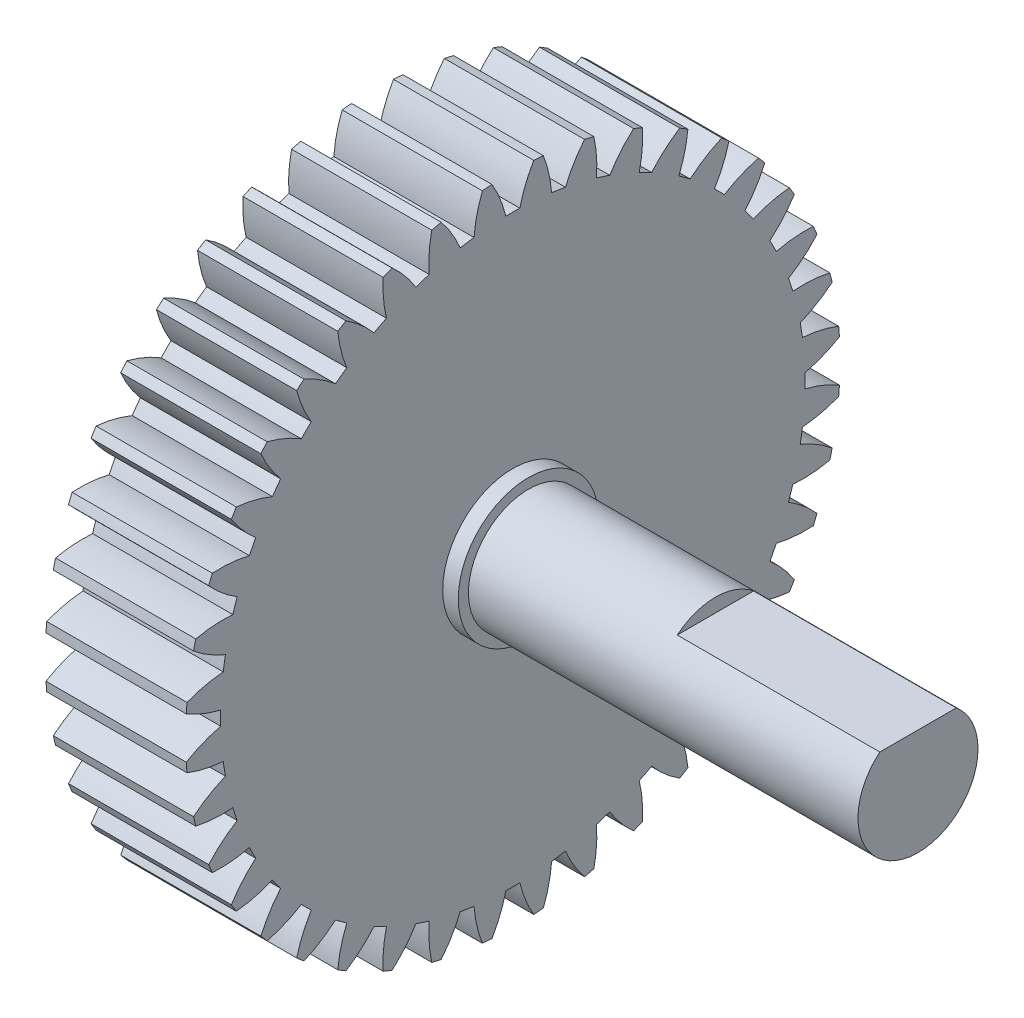
SolidWorks part; units mm, degrees
ref_plane "Plane1" through (0, 0, 0) normal (0, 0, 1) x (1, 0, 0)
ref_plane "Plane2" through (0, 0, 0) normal (0, 1, 0) x (1, 0, 0)
ref_plane "Plane3" through (0, 0, 0) normal (1, 0, 0) x (0, 0, -1)
sketch "HoldingSke" plane through (0, 0, 0) normal (0, 1, 0) x (1, 0, 0)
  line L0 (0, 0) -> (0.766, -0.6428)
  line L1 (-15, 0) -> (100, 0) construction
  line L2 (0, 0) -> (-2.1039, 2.3779)
  line L3 (0, 0) -> (-11.863, 4.5341)
  line L4 (0, 0) -> (6.6156, 5.5511)
  line L5 (0, 0) -> (-46.8476, -17.4728)
  line L6 (0, 0) -> (-7.4607, -5.0337)
  line L7 (-2.1039, 2.3779) -> (8.6586, 51.2059)
  line L8 (-76.2, 54.61) -> (-75.5, 54.61)
  line L9 (-71.009, 38.7566) -> (-53.1078, 45.2721)
  line L10 (-76.2, 71.12) -> (104.1128, 71.12)
  line L11 (0, 0) -> (-9, 0)
  line L12 (-76.2, 101.6) -> (-76.162, 101.6)
  line L13 (24.9733, 27.94) -> (52.9518, 28.4284)
  line L14 (24.9733, 27.94) -> (24.9743, 27.94)
  line L15 (24.9733, 27.94) -> (100.4006, 29.5858)
  line L16 (-63.627, -1) -> (-12.827, -1)
  circle A0 centre (0, 0) radius 2
  circle A1 centre (0, 0) radius 18.749
  circle A2 centre (0, 0) radius 37.5
  circle A3 centre (0, 0) radius 2
  dimension "MHD" = 37.498
  dimension "Hub_dia" = 75
  dimension "Bore" = 4
  dimension "MBD" = 4
  dimension "Num_teeth" = 40
  dimension "Pitch" = 1
  dimension "Overall_len" = 50
  dimension "Show_teeth" = 40
  dimension "Thickness" = 9
  dimension "OAL" = 50.0001
  dimension "T_dim" = 0.7
  dimension "Ap" = 20
  dimension "H" = 19.05
  dimension "Pitch_radius" = 180.3128
  dimension "Width" = 9
  dimension "Backlash" = 0.038
  dimension "Addendum_fac" = 1
  dimension "Dedendum_fac" = 1.25
  dimension "Clearance_fac" = 0.25
  dimension "Dedendum_add" = 0.001
  dimension "Module" = 1
sketch "BasProSke" plane through (0, 0, 0) normal (0, 1, 0) x (1, 0, 0)
  line L0 (-10, 0) -> (60, 0) construction
  line L1 (0, 0) -> (0, 21)
  line L2 (0, 0) -> (9, 0)
  line L3 (9, 0) -> (9, 21)
  line L4 (9, 21) -> (0, 21)
  dimension "Thickness" = 9
  dimension "Diameter" = 42
revolve "Base-Revolve" add sketch "BasProSke" angle 360 about L0
sketch "TooCutSke" plane through (0, 0, 0) normal (1, 0, 0) x (0, 0, -1)
  line L1 (0, 0) -> (0, 107) construction
  line L2 (0, 0) -> (-0.8517, 19.9819) construction
  line L3 (0, 0) -> (-3.1363, 39.8509) construction
  line L4 (-0.8517, 19.9819) -> (-1.5682, 19.9255) construction
  arc A0 (0.4487, 18.7436) -> (-0.4487, 18.7436) centre (0, 0) ccw
  arc A1 (1.3547, 20.9817) -> (-1.3547, 20.9817) centre (0, 0) ccw
  circle A2 centre (0, 0) radius 20 construction
  circle A3 centre (0, 0) radius 18.7939 construction
  arc A4 (-0.4487, 18.7436) -> (-1.3547, 20.9817) centre (-8.2322, 16.895) ccw
  arc A5 (1.3547, 20.9817) -> (0.4487, 18.7436) centre (8.2322, 16.895) ccw
  dimension "Root_dia" = 37.498
  dimension "Overcut_dia" = 42.0508
  dimension "Pitch_dia" = 40
  dimension "Base_dia" = 37.5877
  dimension "Flank_rad" = 8
  dimension "Half_ang" = 4.5
  dimension "Half_CT" = 0.7187
extrude "ToothCut" cut sketch "TooCutSke" along normal through all
fillet "Breaks" [suppressed] radius 0.02 tangent propagation no
fillet "RootFillets" [suppressed] radius 0.251
pattern_circular "TeethCuts" count 40 every 9 about axis through (-10, 0, 0) along (1, 0, 0) of "ToothCut", "RootFillets", "Breaks"
sketch "HubNeaOneSke" plane through (0, 0, 0) normal (-1, 0, 0) x (0, 0, 1)
  circle A0 centre (0, 0) radius 18.749
  dimension "Diameter" = 37.498
extrude "HubNearOne" [suppressed] add sketch "HubNeaOneSke" along normal blind 41.0001
sketch "HubNeaBotSke" plane through (0, 0, 0) normal (-1, 0, 0) x (0, 0, 1)
  circle A0 centre (0, 0) radius 18.749
  dimension "Diameter" = 37.498
extrude "HubNearBoth" [suppressed] add sketch "HubNeaBotSke" along normal blind 20.5
ref_plane "FarPln" through (9, 0, 0) normal (1, 0, 0) x (0, 0, -1)
sketch "HubFarSke" plane through (9, 0, 0) normal (1, 0, 0) x (0, 0, -1)
  circle A0 centre (0, 0) radius 18.749
  dimension "Diameter" = 37.498
extrude "HubFar" [suppressed] add sketch "HubFarSke" along normal blind 20.5
sketch "BorSke" plane through (0, 0, 0) normal (1, 0, 0) x (0, 0, -1)
  circle A0 centre (0, 0) radius 2
  dimension "Diameter" = 4
extrude "Bore" cut sketch "BorSke" along normal mid plane 100.0001
sketch "KeySke" plane through (0, 0, 0) normal (1, 0, 0) x (0, 0, -1)
  line L0 (-0.8, 0) -> (-0.8, 2.7)
  line L1 (-0.8, 2.7) -> (0.8, 2.7)
  line L2 (0.8, 2.7) -> (0.8, 0)
  line L3 (0, 0) -> (0, 34) construction
  line L4 (-0.8, 0) -> (0.8, 0)
  dimension "Offset" = 2.7
  dimension "Width" = 1.6
extrude "Keyway" [suppressed] cut sketch "KeySke" along normal mid plane 100.0001
pattern_circular "Keyway2" [suppressed] count 2 every 90 about axis through (-10, 0, 0) along (1, 0, 0) reverse direction yes
sketch "Sketch1" plane through (9, 0, 0) normal (1, 0, 0) x (0, 0, -1)
  line L0 (-2.45, 2.9698) -> (2.45, 2.9698)
  circle A0 centre (0, 0) radius 4.5
  circle A1 centre (0, 0) radius 3.85
  dimension "D1" = 4.9
  dimension "D2" = 7.7
  dimension "D3" = 9
extrude "Boss-Extrude1" add sketch "Sketch1" along normal blind 26 and the other way blind 9 contours L0 A1 region at (9, -0.2248, 0)
extrude "Boss-Extrude2" add sketch "Sketch1<3>" along normal blind 13 and the other way blind 9 contours L0 A1 region at (9, 3.3256, 0)
sketch "Sketch1<3>" plane through (9, 0, 0) normal (1, 0, 0) x (0, 0, -1) same geometry as "Sketch1"
extrude "Boss-Extrude3" add sketch "Sketch1<4>" along normal blind 1 contours A0 A1 region at (9, 0, 4.3727)
sketch "Sketch1<4>" plane through (9, 0, 0) normal (1, 0, 0) x (0, 0, -1) same geometry as "Sketch1"
equation "' \"Module@HoldingSke\" = 6.35"
equation "' \"Num_teeth@HoldingSke\" = 12"
equation "' \"Ap@HoldingSke\" =  20"
equation "' \"Ap@HoldingSke\" = 20"
equation "' \"Width@HoldingSke\" = 0.5 * 25.4"
equation "' \"Hub_dia@HoldingSke\"= 1 * 25.4"
equation "' \"Hub_dia@HoldingSke\" = 1 * 25.4"
equation "' \"Overall_len@HoldingSke\" = 1.0 * 25.4"
equation "' \"Bore@HoldingSke\" = 0.75 * 25.4"
equation "' \"T_dim@HoldingSke\" = 0.1 * 25.4"
equation "' \"Width@KeySke\" = 0.25 * 25.4"
equation "' \"Show_teeth@HoldingSke\" = 13"
equation "' \"Backlash@HoldingSke\" = 0.009 * 25.4"
equation "' \"Addendum_fac@HoldingSke\" = 1.0"
equation "' \"Dedendum_fac@HoldingSke\" = 1.25"
equation "' \"Dedendum_add@HoldingSke\" = 0.00005 * 25.4"
equation "' \"Clearance_fac@HoldingSke\" = 0.25"
equation "\"Pitch@HoldingSke\" = 1 / \"Module@HoldingSke\""
equation "\"Overcut_dia@TooCutSke\" = (\"Num_teeth@HoldingSke\" + 2 * \"Addendum_fac@HoldingSke\") / \"Pitch@HoldingSke\" + 0.002 * 25.4"
equation "\"Pitch_dia@TooCutSke\" = \"Num_teeth@HoldingSke\" / \"Pitch@HoldingSke\""
equation "\"Base_dia@TooCutSke\" = \"Num_teeth@HoldingSke\" / \"Pitch@HoldingSke\" * cos((\"Ap@HoldingSke\"  * 3.14159265 / 180))"
equation "\"Root_dia@TooCutSke\" = (\"Num_teeth@HoldingSke\" + 2) / \"Pitch@HoldingSke\" - 2 * (\"Addendum_fac@HoldingSke\" + \"Dedendum_fac@HoldingSke\") / \"Pitch@HoldingSke\" - \"Dedendum_add@HoldingSke\" * 2"
equation "\"Half_ang@TooCutSke\" = 180 / \"Num_teeth@HoldingSke\""
equation "\"Half_CT@TooCutSke\" = \"Num_teeth@HoldingSke\" / \"Pitch@HoldingSke\" * sin((3.14159265 / 2 / \"Num_teeth@HoldingSke\")) / 2 - 7 * \"Backlash@HoldingSke\" / 4"
equation "\"Flank_rad@TooCutSke\" = \"Num_teeth@HoldingSke\" / \"Pitch@HoldingSke\" / 5"
equation "\"Radius@RootFillets\" = \"Clearance_fac@HoldingSke\" / \"Pitch@HoldingSke\" + \"Dedendum_add@HoldingSke\""
equation "\"Break_rad@Breaks\" = 0.02 / \"Pitch@HoldingSke\""
equation "\"Thickness@HoldingSke\" = \"Width@HoldingSke\""
equation "\"OAL@HoldingSke\" = \"Thickness@HoldingSke\""
equation "\"MHD@HoldingSke\" = (\"Num_teeth@HoldingSke\" + 2) / \"Pitch@HoldingSke\" - 2 * (\"Addendum_fac@HoldingSke\" + \"Dedendum_fac@HoldingSke\")  / \"Pitch@HoldingSke\" - \"Dedendum_add@HoldingSke\" * 2"
equation "\"MBD@HoldingSke\" = (\"Num_teeth@HoldingSke\" + 2) / \"Pitch@HoldingSke\" - 2 * (\"Addendum_fac@HoldingSke\" + \"Dedendum_fac@HoldingSke\")  / \"Pitch@HoldingSke\" - \"Dedendum_add@HoldingSke\" * 2 - 0.002 * 25.4"
equation "\"MHD@HoldingSke\" = ((sgn( \"MHD@HoldingSke\" - \"Hub_dia@HoldingSke\" )-1)*( \"MHD@HoldingSke\" - \"Hub_dia@HoldingSke\" ))/-2+ \"Hub_dia@HoldingSke\""
equation "\"MBD@HoldingSke\" = ((sgn( \"MBD@HoldingSke\" - \"Bore@HoldingSke\" )-1)*( \"MBD@HoldingSke\" - \"Bore@HoldingSke\" ))/-2+ \"Bore@HoldingSke\""
equation "\"OAL@HoldingSke\" = ((sgn( \"OAL@HoldingSke\" - \"Overall_len@HoldingSke\" )+1)*( \"OAL@HoldingSke\" - \"Overall_len@HoldingSke\" ))/2 + \"Overall_len@HoldingSke\" + 0.000002 * 25.4"
equation "\"Num_teeth@TeethCuts\" = int( \"Show_teeth@HoldingSke\" ) + 1"
equation "\"Num_teeth@TeethCuts\" = ((sgn( \"Num_teeth@TeethCuts\" - \"Num_teeth@HoldingSke\" )-1)*( \"Num_teeth@TeethCuts\" - \"Num_teeth@HoldingSke\" ))/-2+ \"Num_teeth@HoldingSke\""
equation "\"Num_teeth@TeethCuts\" = ((sgn( \"Num_teeth@TeethCuts\" - 2.0)+1)*( \"Num_teeth@TeethCuts\" - 2.0))/2 +2.0"
equation "\"Angle@TeethCuts\" = 360.0 / \"Num_teeth@HoldingSke\""
equation "\"Diameter@BasProSke\" = (\"Num_teeth@HoldingSke\" + 2 * \"Addendum_fac@HoldingSke\") / \"Pitch@HoldingSke\""
equation "\"Thickness@BasProSke\"  = \"Thickness@HoldingSke\""
equation "' \"Fillet_rad@BasProSke\" =  \"Thickness@HoldingSke\" * 0.05"
equation "' \"Fillet_rad@BasProSke\" = \"Thickness@HoldingSke\" * 0.05"
equation "\"MHD@HoldingSke\" = ((sgn( \"MHD@HoldingSke\" - \"Root_dia@TooCutSke\" )-1)*( \"MHD@HoldingSke\" - \"Root_dia@TooCutSke\" ))/-2+ \"Root_dia@TooCutSke\""
equation "\"Diameter@HubNeaOneSke\" = \"MHD@HoldingSke\""
equation "\"Length@HubNearOne\" = \"OAL@HoldingSke\" - \"Thickness@BasProSke\""
equation "\"Diameter@HubNeaBotSke\" = \"MHD@HoldingSke\""
equation "\"Length@HubNearBoth\" = ( \"OAL@HoldingSke\" - \"Thickness@BasProSke\" ) / 2.0"
equation "\"Thickness@FarPln\" = \"Thickness@BasProSke\""
equation "\"Diameter@HubFarSke\" = \"MHD@HoldingSke\""
equation "\"Length@HubFar\" = ( \"OAL@HoldingSke\" - \"Thickness@BasProSke\" ) / 2.0"
equation "\"Diameter@BorSke\" = \"MBD@HoldingSke\""
equation "\"D1@Bore\" = \"OAL@HoldingSke\" * 2.0"
equation "\"D1@Keyway\" = \"OAL@HoldingSke\" * 2.0"
equation "\"Offset@KeySke\" = \"T_dim@HoldingSke\" + \"MBD@HoldingSke\" / 2.0"
